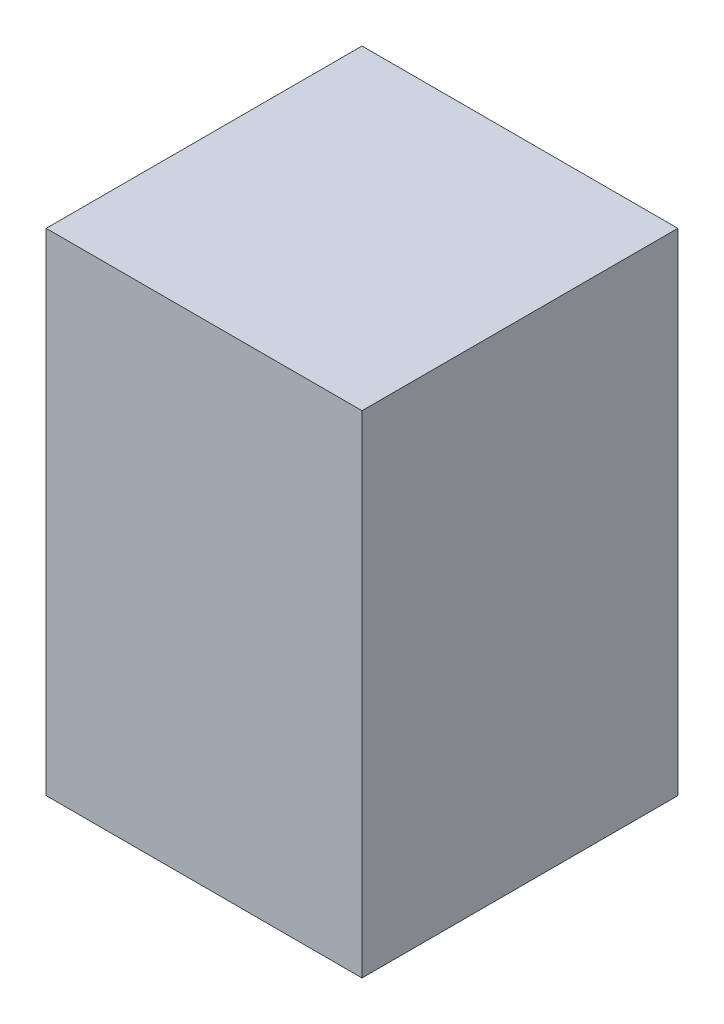
SolidWorks part; units mm, degrees
ref_plane "Front Plane" through (0, 0, 0) normal (0, 0, 1) x (1, 0, 0)
ref_plane "Top Plane" through (0, 0, 0) normal (0, 1, 0) x (1, 0, 0)
ref_plane "Right Plane" through (0, 0, 0) normal (1, 0, 0) x (0, 0, -1)
sketch "Sketch1" plane through (0, 0, 0) normal (0, 1, 0) x (1, 0, 0)
  line L1 (-28.575, -28.575) -> (28.575, -28.575)
  line L2 (-28.575, -28.575) -> (-28.575, 28.575)
  line L3 (-28.575, 28.575) -> (28.575, 28.575)
  line L4 (28.575, -28.575) -> (28.575, 28.575)
  line L5 (-28.575, -28.575) -> (28.575, 28.575) construction
  line L6 (-28.575, 28.575) -> (28.575, -28.575) construction
  point P0 (0, 0)
  dimension "D1" = 57.15
  dimension "D2" = 57.15
extrude "Boss-Extrude1" add sketch "Sketch1" along normal blind 44.45 and the other way blind 44.45
